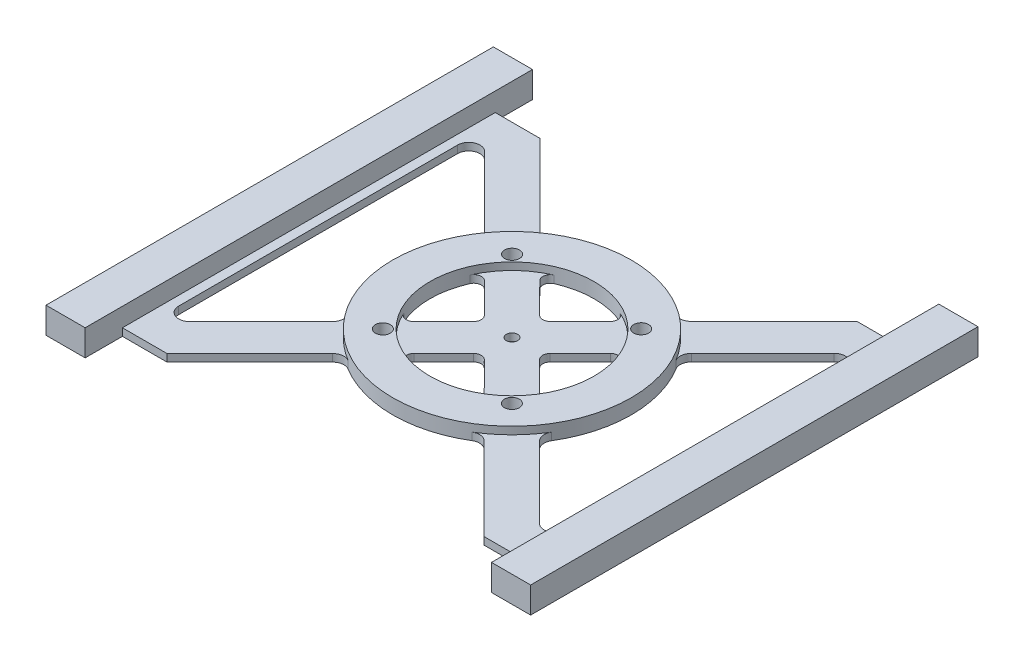
SolidWorks part; units mm, degrees
ref_plane "Front Plane" through (0, 0, 0) normal (0, 0, 1) x (1, 0, 0)
ref_plane "Top Plane" through (0, 0, 0) normal (0, 1, 0) x (1, 0, 0)
ref_plane "Right Plane" through (0, 0, 0) normal (1, 0, 0) x (0, 0, -1)
sketch "Sketch1" plane through (0, 0, 0) normal (0, 1, 0) x (1, 0, 0)
  circle A0 centre (0, 0) radius 22
  circle A1 centre (0, 0) radius 22
  circle A2 centre (0, 0) radius 32
  dimension "D1" = 44
  dimension "D2" = 44
  dimension "D3" = 64
extrude "Boss-Extrude2" add sketch "Sketch1" along normal blind 4 contours A2 A0 region at (-31.0949, 0, 0)
sketch "Sketch3" plane through (0, 0, 0) normal (0, 1, 0) x (1, 0, 0)
  line L1 (-65, -60) -> (-54.5, -60)
  line L2 (-65, -60) -> (-65, 60)
  line L3 (-65, 60) -> (-54.5, 60)
  line L4 (-54.5, -60) -> (-54.5, 60)
  line L5 (54.5, -60) -> (65, -60)
  line L6 (54.5, -60) -> (54.5, 60)
  line L7 (54.5, 60) -> (65, 60)
  line L8 (65, -60) -> (65, 60)
  point P8 (54.5, 0)
  point P10 (-54.5, 0)
  dimension "D1" = 120
  dimension "D2" = 10.5
  dimension "D3" = 130
  dimension "D4" = 10.5
  dimension "D5" = 54.5
  dimension "D6" = 120
extrude "Boss-Extrude4" add sketch "Sketch3" along normal blind 7 separate body
sketch "Sketch4" plane through (0, 0, 0) normal (0, 1, 0) x (1, 0, 0)
  line L0 (-54.5, 50) -> (-42.5, 50)
  line L1 (-54.5, -60) -> (-54.5, 60) construction
  line L2 (-42.5, 50) -> (-20.3164, 27.7803)
  line L3 (54.5, -50) -> (42.5, -50)
  line L4 (54.5, 60) -> (54.5, -60) construction
  line L5 (42.5, -50) -> (20.3164, -27.7803)
  line L6 (-54.5, 60) -> (-65, 60) construction
  line L7 (54.5, -60) -> (65, -60) construction
  line L8 (-52, -37.4031) -> (-52, 37.4031)
  line L9 (52, -37.4031) -> (52, 37.4031)
  line L10 (-54.5, -50) -> (-42.5, -50)
  line L11 (-54.5, -60) -> (-54.5, 60) construction
  line L12 (54.5, 50) -> (42.5, 50)
  line L13 (42.5, 50) -> (20.3164, 27.7803)
  line L14 (-42.5, -50) -> (-20.3164, -27.7803)
  line L15 (-8.8293, -1.4131) -> (-16.8848, -9.4817)
  line L16 (8.8293, -1.4131) -> (16.8848, -9.4817)
  line L17 (8.8293, 1.4131) -> (16.8848, 9.4817)
  line L18 (-8.8293, 1.4131) -> (-16.8848, 9.4817)
  line L19 (-27.7471, 20.3617) -> (-46.877, 39.5227)
  line L20 (-9.4542, 16.9003) -> (-1.4154, 8.8484)
  line L21 (9.4542, 16.9003) -> (1.4154, 8.8484)
  line L22 (27.7471, 20.3617) -> (46.877, 39.5227)
  line L23 (27.7471, -20.3617) -> (46.877, -39.5227)
  line L24 (9.4542, -16.9003) -> (1.4154, -8.8484)
  line L25 (-9.4542, -16.9003) -> (-1.4154, -8.8484)
  line L26 (-27.7471, -20.3617) -> (-46.877, -39.5227)
  line L27 (-54.5, -50) -> (-54.5, 50)
  line L28 (54.5, -50) -> (54.5, 50)
  arc A0 (46.877, -39.5227) -> (52, -37.4031) centre (49, -37.4031) ccw
  arc A1 (46.877, 39.5227) -> (52, 37.4031) centre (49, 37.4031) cw
  arc A2 (-52, 37.4031) -> (-46.877, 39.5227) centre (-49, 37.4031) cw
  arc A3 (-46.877, -39.5227) -> (-52, -37.4031) centre (-49, -37.4031) cw
  arc A4 (-16.634, -27.337) -> (16.634, -27.337) centre (0, 0) ccw
  arc A5 (-8.8427, -20.1447) -> (8.8427, -20.1447) centre (0, 0) ccw
  arc A6 (20.1302, -8.8755) -> (20.1302, 8.8755) centre (0, 0) ccw
  arc A7 (27.3099, -16.6785) -> (27.3099, 16.6785) centre (0, 0) ccw
  arc A8 (8.8427, 20.1447) -> (-8.8427, 20.1447) centre (0, 0) ccw
  arc A9 (16.634, 27.337) -> (-16.634, 27.337) centre (0, 0) ccw
  arc A10 (-20.1302, 8.8755) -> (-20.1302, -8.8755) centre (0, 0) ccw
  arc A11 (-27.3099, 16.6785) -> (-27.3099, -16.6785) centre (0, 0) ccw
  arc A12 (-16.634, -27.337) -> (-20.3164, -27.7803) centre (-18.1934, -29.8998) ccw
  arc A13 (16.634, -27.337) -> (20.3164, -27.7803) centre (18.1934, -29.8998) cw
  arc A14 (27.3099, -16.6785) -> (27.7471, -20.3617) centre (29.8702, -18.2421) ccw
  arc A15 (27.3099, 16.6785) -> (27.7471, 20.3617) centre (29.8702, 18.2421) cw
  arc A16 (16.634, 27.337) -> (20.3164, 27.7803) centre (18.1934, 29.8998) ccw
  arc A17 (-16.634, 27.337) -> (-20.3164, 27.7803) centre (-18.1934, 29.8998) cw
  arc A18 (-27.3099, 16.6785) -> (-27.7471, 20.3617) centre (-29.8702, 18.2421) ccw
  arc A19 (-27.7471, -20.3617) -> (-27.3099, -16.6785) centre (-29.8702, -18.2421) ccw
  arc A20 (8.8427, 20.1447) -> (9.4542, 16.9003) centre (8.0388, 18.3133) cw
  arc A21 (20.1302, 8.8755) -> (16.8848, 9.4817) centre (18.3002, 8.0686) ccw
  arc A22 (20.1302, -8.8755) -> (16.8848, -9.4817) centre (18.3002, -8.0686) cw
  arc A23 (8.8427, -20.1447) -> (9.4542, -16.9003) centre (8.0388, -18.3133) ccw
  arc A24 (-8.8427, -20.1447) -> (-9.4542, -16.9003) centre (-8.0388, -18.3133) cw
  arc A25 (-16.8848, -9.4817) -> (-20.1302, -8.8755) centre (-18.3002, -8.0686) cw
  arc A26 (-20.1302, 8.8755) -> (-16.8848, 9.4817) centre (-18.3002, 8.0686) cw
  arc A27 (-8.8427, 20.1447) -> (-9.4542, 16.9003) centre (-8.0388, 18.3133) ccw
  arc A28 (-1.4154, -8.8484) -> (1.4154, -8.8484) centre (0, -10.2614) cw
  arc A29 (8.8293, -1.4131) -> (8.8293, 1.4131) centre (10.2447, 0) cw
  arc A30 (1.4154, 8.8484) -> (-1.4154, 8.8484) centre (0, 10.2614) cw
  arc A31 (-8.8293, -1.4131) -> (-8.8293, 1.4131) centre (-10.2447, 0) ccw
  point P52 (-94.3848, 26.0483)
  point P59 (26.018, -18.6297)
  point P62 (26.018, 18.6297)
  point P69 (-26.018, 18.6297)
  point P72 (-26.018, -18.6297)
  point P75 (11.3793, 18.8285)
  point P82 (11.3793, -18.8285)
  point P85 (-11.3793, -18.8285)
  point P92 (-11.3793, 18.8285)
  point P97 (7.4186, 0)
  point P102 (-7.4186, 0)
  dimension "D9" = 3
  dimension "D10" = 44
  dimension "D11" = 64
  dimension "D12" = 3
  dimension "D13" = 2
  dimension "D1" = 10.5
  dimension "D2" = 10
  dimension "D3" = 10
  dimension "D4" = 2.5
  dimension "D5" = 2.5
  dimension "D6" = 12
  dimension "D7" = 12
  dimension "D8" = 10.5
extrude "Boss-Extrude5" add sketch "Sketch4" along normal blind 2 contours L28 L12 L13 A16 A9 A17 L2 L0 L27 L10 L14 A12 A4 A13 L5 L3 | A3 L8 A2 L19 A18 A11 A19 L26 | A0 L9 A1 L22 A15 A7 A14 L23 | L17 A21 A6 A22 L16 A29 | A31 L18 A26 A10 A25 L15 | A30 L21 A20 A8 A27 L20 | L24 A28 L25 A24 A5 A23
sketch "Sketch5" plane through (0, 2, 0) normal (0, 1, 0) x (1, 0, 0)
  circle A0 centre (0, 0) radius 1.5
  dimension "D1" = 3
extrude "Cut-Extrude1" cut sketch "Sketch5" against normal blind 4
sketch "Sketch6" plane through (0, 0, 0) normal (0, -1, 0) x (1, 0, 0)
  line L1 (-27.7471, 20.3617) -> (-46.877, 39.5227) construction
  line L2 (42.5, 50) -> (20.3164, 27.7803) construction
  line L3 (27.7471, -20.3617) -> (46.877, -39.5227) construction
  circle A0 centre (-17.31, -17.3382) radius 2
  circle A1 centre (17.31, -17.3382) radius 2
  circle A2 centre (17.31, 17.3382) radius 2
  circle A3 centre (-17.31, 17.3382) radius 2
  circle A5 centre (0, 0) radius 1.5 construction
  dimension "D5" = 4
  dimension "D6" = 4
  dimension "D7" = 4
  dimension "D8" = 4
  dimension "D1" = 24.5
  dimension "D2" = 5.25
  dimension "D3" = 5.25
  dimension "D4" = 5.25
extrude "Cut-Extrude2" cut sketch "Sketch6" against normal blind 4
